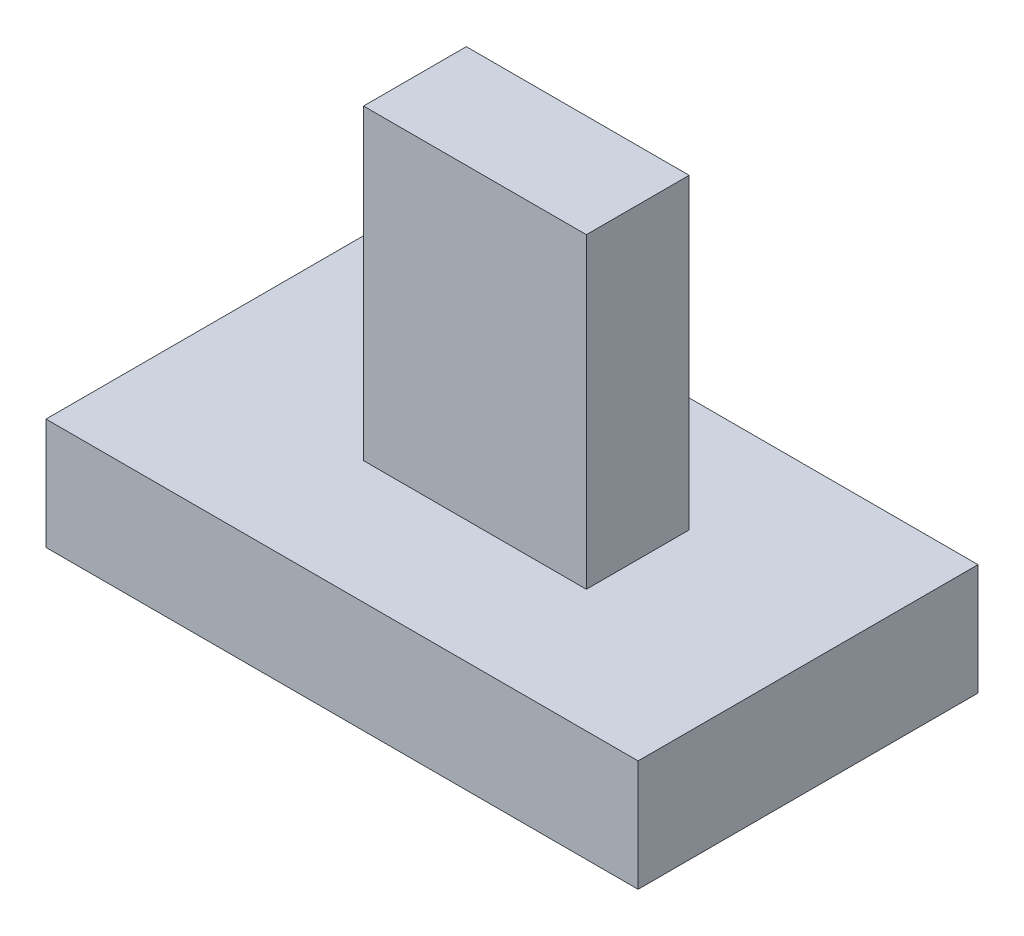
SolidWorks part; units mm, degrees
other "DetailItem1"
other "Weld Folder"
other "Weld Bead1"
ref_plane "Front Plane" through (0, 0, 0) normal (0, 0, 1) x (1, 0, 0)
ref_plane "Top Plane" through (0, 0, 0) normal (0, 1, 0) x (1, 0, 0)
ref_plane "Right Plane" through (0, 0, 0) normal (1, 0, 0) x (0, 0, -1)
other "Configuration Table"
sketch "Sketch2" plane through (0, 0, 0) normal (0, 1, 0) x (1, 0, 0)
  line L1 (-45.9668, 25.6676) -> (44.6247, 25.6676)
  line L2 (-45.9668, 25.6676) -> (-45.9668, -26.3386)
  line L3 (-45.9668, -26.3386) -> (44.6247, -26.3386)
  line L4 (44.6247, 25.6676) -> (44.6247, -26.3386)
extrude "Boss-Extrude1" add sketch "Sketch2" along normal blind 17.018
sketch "Sketch4" plane through (0, 17.018, 0) normal (0, 1, 0) x (1, 0, 0)
  line L1 (-16.1637, 8.17) -> (17.9278, 8.17)
  line L2 (-16.1637, 8.17) -> (-16.1637, -7.5589)
  line L3 (-16.1637, -7.5589) -> (17.9278, -7.5589)
  line L4 (17.9278, 8.17) -> (17.9278, -7.5589)
extrude "Cut-Extrude2" cut sketch "Sketch4" against normal blind 46.99
extrude "Boss-Extrude2" add sketch "Sketch4<2>" along normal blind 46.99
sketch "Sketch4<2>" plane through (0, 17.018, 0) normal (0, 1, 0) x (1, 0, 0) same geometry as "Sketch4"
